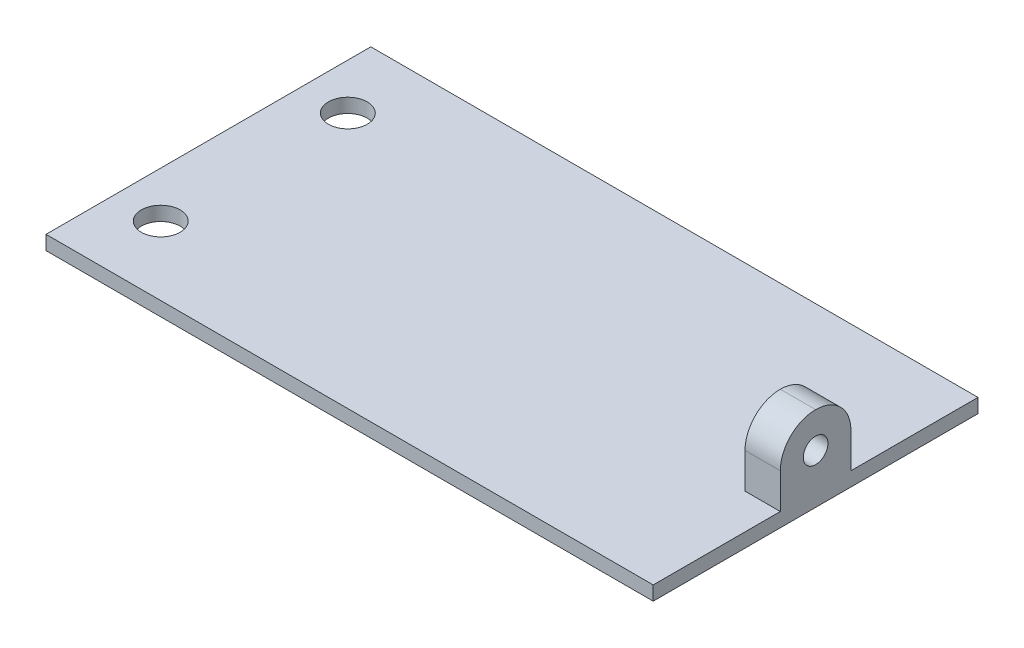
SolidWorks part; units mm, degrees
ref_plane "Front Plane" through (0, 0, 0) normal (0, 0, 1) x (1, 0, 0)
ref_plane "Top Plane" through (0, 0, 0) normal (0, 1, 0) x (1, 0, 0)
ref_plane "Right Plane" through (0, 0, 0) normal (1, 0, 0) x (0, 0, -1)
sketch "Sketch1" plane through (0, 0, 0) normal (0, 1, 0) x (1, 0, 0)
  line L1 (-43, -23) -> (43, -23)
  line L2 (-43, -23) -> (-43, 23)
  line L3 (-43, 23) -> (43, 23)
  line L4 (43, -23) -> (43, 23)
  line L5 (-43, -23) -> (43, 23) construction
  line L6 (-43, 23) -> (43, -23) construction
  point P0 (0, 0)
  dimension "D1" = 86
  dimension "D2" = 46
extrude "Boss-Extrude1" add sketch "Sketch1" along normal blind 2
sketch "Sketch2" plane through (0, 2, 0) normal (0, 1, 0) x (1, 0, 0)
  line L0 (-43, 0) -> (-36.5, 0) construction
  line L1 (-43, 23) -> (-43, -23) construction
  line L2 (-36.5, -13.25) -> (-36.5, 13.25) construction
  circle A0 centre (-36.5, 13.25) radius 2.75
  circle A1 centre (-36.5, -13.25) radius 2.75
  point P8 (-36.5, 0)
  dimension "D3" = 5.5
  dimension "D1" = 6.5
  dimension "D2" = 26.5
extrude "Cut-Extrude1" cut sketch "Sketch2" against normal up to next
sketch "Sketch3" plane through (0, 2, 0) normal (0, 1, 0) x (1, 0, 0)
  line L0 (43, 0) -> (38, 0) construction
  line L1 (43, -23) -> (43, 23) construction
  line L7 (38, -5) -> (38, 5)
  line L8 (38, 5) -> (43, 5)
  line L9 (43, 5) -> (43, -5)
  line L10 (43, -5) -> (38, -5)
  point P8 (38, 0)
  point P10 (38, 0)
  dimension "D1" = 5
  dimension "D2" = 10
extrude "Boss-Extrude2" add sketch "Sketch3" along normal blind 10
sketch "Sketch4" plane through (43, 0, 0) normal (1, 0, 0) x (0, 0, -1)
  line L0 (-5, 2) -> (5, 2) construction
  line L1 (0, 2) -> (0, 12) construction
  line L2 (-5, 12) -> (5, 12) construction
  circle A0 centre (0, 7) radius 1.75
  dimension "D1" = 3.5
extrude "Cut-Extrude2" cut sketch "Sketch4" against normal blind 10
fillet "Fillet1" radius 5 2 edges at (40.5, 12, -5) (40.5, 12, 5)
